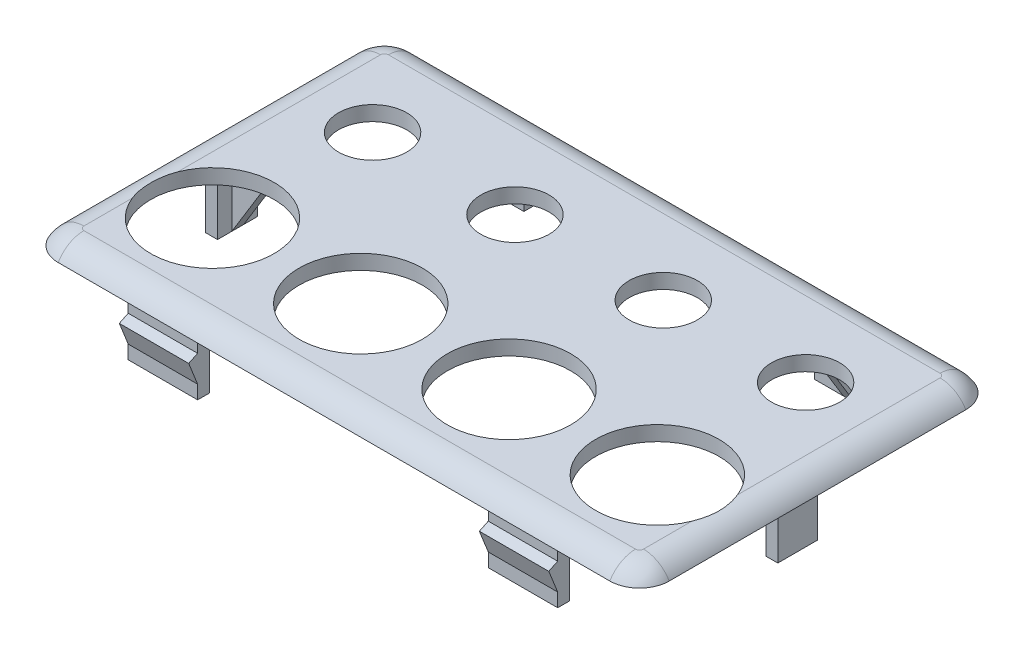
SolidWorks part; units mm, degrees
ref_plane "Front Plane" through (0, 0, 0) normal (0, 0, 1) x (1, 0, 0)
ref_plane "Top Plane" through (0, 0, 0) normal (0, 1, 0) x (1, 0, 0)
ref_plane "Right Plane" through (0, 0, 0) normal (1, 0, 0) x (0, 0, -1)
sketch "Sketch1" plane through (0, 0, 0) normal (0, 1, 0) x (1, 0, 0)
  line L1 (-46.5, 30) -> (46.5, 30)
  line L2 (-51.5, 25) -> (-51.5, -25)
  line L3 (-46.5, -30) -> (46.5, -30)
  line L4 (51.5, 25) -> (51.5, -25)
  line L5 (-51.5, 30) -> (51.5, -30) construction
  line L6 (-51.5, -30) -> (51.5, 30) construction
  arc A0 (46.5, -30) -> (51.5, -25) centre (46.5, -25) ccw
  arc A1 (51.5, 25) -> (46.5, 30) centre (46.5, 25) ccw
  arc A2 (-46.5, -30) -> (-51.5, -25) centre (-46.5, -25) cw
  arc A3 (-46.5, 30) -> (-51.5, 25) centre (-46.5, 25) ccw
  point P0 (0, 0)
  dimension "D3" = 5
  dimension "D1" = 103
  dimension "D2" = 60
extrude "Boss-Extrude1" add sketch "Sketch1" along normal blind 2.5
fillet "Fillet1" radius 5 8 edges at (-50.0355, 2.5, -28.5355) (0, 2.5, -30) (50.0355, 2.5, -28.5355) (51.5, 2.5, 0) (50.0355, 2.5, 28.5355) (0, 2.5, 30) (-50.0355, 2.5, 28.5355) (-51.5, 2.5, 0)
sketch "Sketch2" plane through (0, 0, 0) normal (0, -1, 0) x (1, 0, 0)
  line L0 (0, 30) -> (0, -30) construction
  line L1 (-36.2, 28.5) -> (-24.5, 28.5)
  line L2 (-36.2, 28.5) -> (-36.2, 26.5)
  line L3 (-36.2, 26.5) -> (-31.35, 26.5)
  line L4 (-24.5, 28.5) -> (-24.5, 26.5)
  line L5 (-46.5, 30) -> (46.5, 30) construction
  line L6 (46.5, -30) -> (-46.5, -30) construction
  line L7 (-51.5, 0) -> (51.5, 0) construction
  line L8 (-51.5, -25) -> (-51.5, 25) construction
  line L9 (51.5, 25) -> (51.5, -25) construction
  line L10 (48.225, -3.2828) -> (46.225, -3.2828)
  line L11 (24.5, 28.5) -> (36.2, 28.5)
  line L12 (24.5, 28.5) -> (24.5, 26.5)
  line L13 (24.5, 26.5) -> (29.35, 26.5)
  line L14 (36.2, 28.5) -> (36.2, 26.5)
  line L15 (24.5, -26.5) -> (29.35, -26.5)
  line L16 (24.5, -26.5) -> (24.5, -28.5)
  line L17 (24.5, -28.5) -> (36.2, -28.5)
  line L18 (36.2, -26.5) -> (36.2, -28.5)
  line L19 (-36.2, -28.5) -> (-24.5, -28.5)
  line L20 (-36.2, -28.5) -> (-36.2, -26.5)
  line L21 (-36.2, -26.5) -> (-31.35, -26.5)
  line L22 (-24.5, -28.5) -> (-24.5, -26.5)
  line L23 (-48.225, 3.4172) -> (-46.225, 3.4172)
  line L24 (-48.225, 3.4172) -> (-48.225, -3.2828)
  line L25 (-48.225, -3.2828) -> (-46.225, -3.2828)
  line L26 (-46.225, 3.4172) -> (-46.225, 1)
  line L27 (46.225, 3.4172) -> (46.225, 1)
  line L28 (48.225, 3.4172) -> (46.225, 3.4172)
  line L29 (48.225, 3.4172) -> (48.225, -3.2828)
  line L30 (-46.225, -0.9998) -> (-46.225, -3.2828)
  line L31 (-46.225, 1) -> (-40.225, 1)
  line L33 (-46.225, -0.9998) -> (-40.225, -0.9998)
  line L34 (-40.225, 1) -> (-40.225, -0.9998)
  line L35 (40.225, 1) -> (40.225, -0.9998)
  line L36 (46.225, 1) -> (40.225, 1)
  line L37 (46.225, -0.9998) -> (40.225, -0.9998)
  line L38 (46.225, -0.9998) -> (46.225, -3.2828)
  line L39 (-30.35, 28.5) -> (-30.35, -31.9661) construction
  line L40 (30.35, 28.5) -> (30.35, -35.5794) construction
  line L41 (-29.35, 26.5) -> (-24.5, 26.5)
  line L43 (-31.35, 26.5) -> (-31.35, 20.5)
  line L44 (-31.35, 20.5) -> (-29.35, 20.5)
  line L45 (-29.35, 26.5) -> (-29.35, 20.5)
  line L46 (-29.35, -26.5) -> (-24.5, -26.5)
  line L48 (-31.35, -26.5) -> (-31.35, -20.5)
  line L49 (-31.35, -20.5) -> (-29.35, -20.5)
  line L50 (-29.35, -26.5) -> (-29.35, -20.5)
  line L51 (31.35, -26.5) -> (36.2, -26.5)
  line L53 (29.35, 26.5) -> (29.35, 20.5)
  line L54 (29.35, 20.5) -> (31.35, 20.5)
  line L55 (31.35, 26.5) -> (31.35, 20.5)
  line L57 (29.35, -26.5) -> (29.35, -20.5)
  line L58 (29.35, -20.5) -> (31.35, -20.5)
  line L59 (31.35, -26.5) -> (31.35, -20.5)
  line L60 (31.35, 26.5) -> (36.2, 26.5)
  dimension "D1" = 2
  dimension "D2" = 11.7
  dimension "D3" = 2
  dimension "D4" = 11.7
  dimension "D5" = 49
  dimension "D6" = 24.5
  dimension "D7" = 24.5
  dimension "D8" = 15.3
  dimension "D9" = 2
  dimension "D11" = 26.5
  dimension "D12" = 2
  dimension "D13" = 11.7
  dimension "D14" = 49
  dimension "D15" = 24.5
  dimension "D16" = 2
  dimension "D17" = 6.7
  dimension "D18" = 46.225
  dimension "D19" = 6
  dimension "D20" = 1.9998
  dimension "D21" = 1
  dimension "D22" = 6
  dimension "D23" = 1
  dimension "D24" = 2
  dimension "D25" = 6
  dimension "D26" = 2
  dimension "D27" = 1
  dimension "D28" = 6
  dimension "D29" = 2
  dimension "D30" = 1
  dimension "D31" = 2
  dimension "D32" = 1
  dimension "D33" = 6
extrude "Boss-Extrude2" add sketch "Sketch2" along normal blind 9.8
sketch "Sketch4" plane through (0, 0, -0.9998) normal (0, 0, -1) x (-1, 0, 0)
  line L0 (40.225, 0) -> (46.225, -9.8)
  line L1 (46.225, -9.8) -> (40.225, -9.8)
  line L2 (40.225, -9.8) -> (40.225, 0)
extrude "Cut-Extrude1" cut sketch "Sketch4" against normal blind 9.8
mirror "Mirror1" about plane through (0, 0, 0) normal (1, 0, 0) of "Cut-Extrude1"
sketch "Sketch5" plane through (-31.35, 0, 0) normal (-1, 0, 0) x (0, 0, 1)
  line L0 (-26.5, -9.8) -> (-20.5, 0)
  line L1 (-20.5, 0) -> (-20.5, -9.8)
  line L2 (-20.5, -9.8) -> (-26.5, -9.8)
extrude "Cut-Extrude2" cut sketch "Sketch5" against normal through all
mirror "Mirror2" about plane through (0, 0, 0) normal (0, 0, 1) of "Cut-Extrude2"
sketch "Sketch6" plane through (36.2, 0, 0) normal (1, 0, 0) x (0, 0, -1)
  line L0 (-28.5, -3) -> (-28.5, -7.5)
  line L1 (-28.5, -9.8) -> (-28.5, 0) construction
  line L2 (-28.5, -3) -> (-30, -3.7261)
  line L3 (-30, -3.7261) -> (-28.5, -7.5)
  dimension "D1" = 4.5
  dimension "D2" = 1.5
  dimension "D3" = 3
extrude "Boss-Extrude3" add sketch "Sketch6" against normal blind 11.7
mirror "Mirror3" about plane through (0, 0, 0) normal (1, 0, 0) of "Boss-Extrude3"
mirror "Mirror4" about plane through (0, 0, 0) normal (0, 0, 1) of "Mirror3"
sketch "Sketch7" plane through (0, 0, 0) normal (0, -1, 0) x (1, 0, 0)
  line L0 (-51.5, 0) -> (51.5, 0) construction
  line L1 (-51.5, -25) -> (-51.5, 25) construction
  line L2 (51.5, 25) -> (51.5, -25) construction
  line L3 (0, 30) -> (0, -30) construction
  line L4 (-46.5, 30) -> (46.5, 30) construction
  line L5 (46.5, -30) -> (-46.5, -30) construction
  circle A0 centre (-37.5, 13) radius 10.4
  circle A1 centre (-12.5, 13) radius 10.4
  circle A2 centre (-36.5, -13) radius 5.75
  circle A4 centre (12.5, 13) radius 10.4
  circle A5 centre (37.5, 13) radius 10.4
  circle A6 centre (-12.5, -13) radius 5.75
  circle A7 centre (12.5, -13) radius 5.75
  circle A8 centre (36.5, -13) radius 5.75
  dimension "D1" = 20.8
  dimension "D2" = 20.8
  dimension "D3" = 11.5
  dimension "D4" = 15
  dimension "D13" = 20.8
  dimension "D16" = 20.8
  dimension "D6" = 11.5
  dimension "D5" = 14
  dimension "D7" = 25
  dimension "D9" = 13
  dimension "D11" = 13
  dimension "D12" = 13
  dimension "D14" = 25
  dimension "D15" = 13
  dimension "D17" = 25
  dimension "D18" = 13
extrude "Cut-Extrude3" cut sketch "Sketch7" against normal through all both and the other way through all
